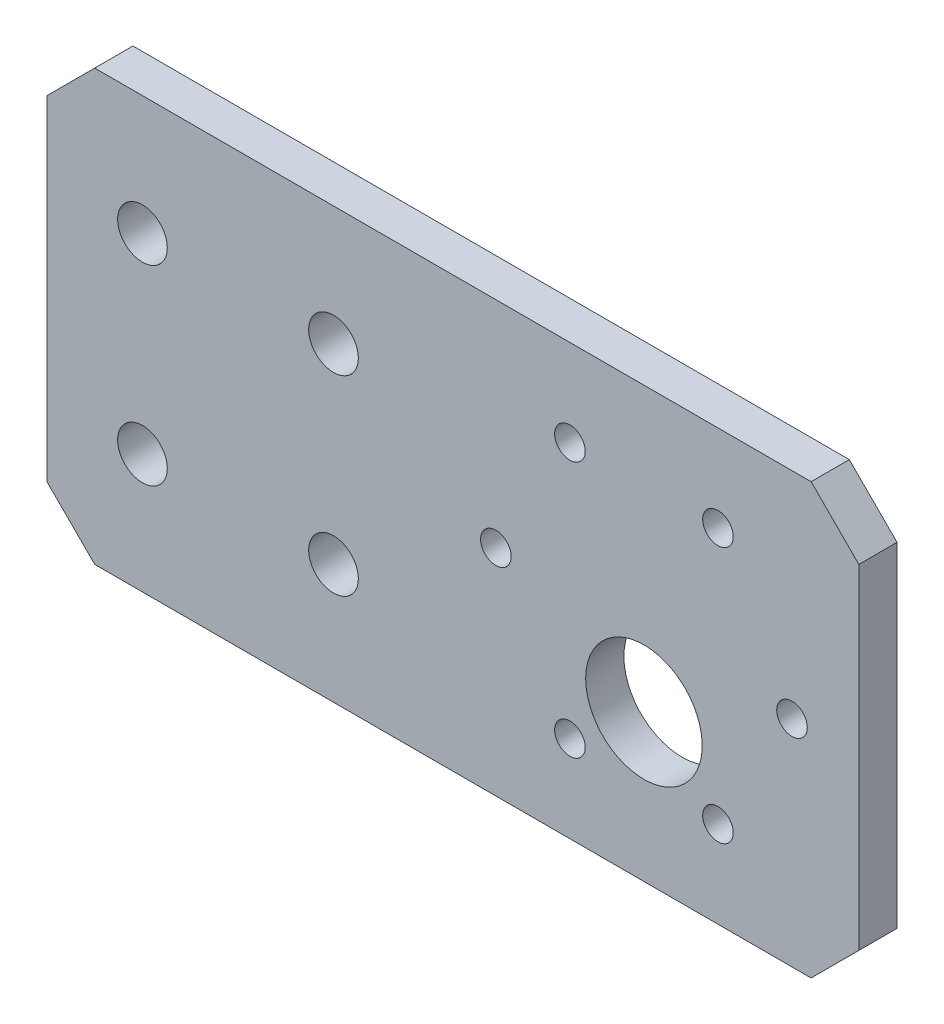
SolidWorks part; units mm, degrees
material "AISI 304"
ref_plane "前基準面" through (0, 0, 0) normal (0, 0, 1) x (1, 0, 0)
ref_plane "上基準面" through (0, 0, 0) normal (0, 1, 0) x (1, 0, 0)
ref_plane "右基準面" through (0, 0, 0) normal (1, 0, 0) x (0, 0, -1)
sketch "Sketch1" plane through (0, 0, 0) normal (0, 0, 1) x (1, 0, 0)
  line L1 (-42.5, -22.5) -> (42.5, -22.5)
  line L2 (-42.5, -22.5) -> (-42.5, 22.5)
  line L3 (-42.5, 22.5) -> (42.5, 22.5)
  line L4 (42.5, -22.5) -> (42.5, 22.5)
  line L5 (-42.5, -22.5) -> (42.5, 22.5) construction
  line L6 (-42.5, 22.5) -> (42.5, -22.5) construction
  point P0 (0, 0)
  dimension "D1" = 45
  dimension "D2" = 85
extrude "Boss-Extrude1" add sketch "Sketch1" along normal blind 4
sketch "Sketch2" plane through (0, 0, 4) normal (0, 0, 1) x (1, 0, 0)
  line L0 (20, 0) -> (20, 22.5) construction
  line L3 (20, 0) -> (35.5, 0) construction
  line L4 (42.5, 22.5) -> (-42.5, 22.5) construction
  line L6 (42.5, -22.5) -> (42.5, 22.5) construction
  circle A4 centre (35.5, 0) radius 1.6
  circle A6 centre (27.75, -13.4234) radius 1.6
  circle A7 centre (12.25, -13.4234) radius 1.6
  circle A8 centre (4.5, 0) radius 1.6
  circle A9 centre (12.25, 13.4234) radius 1.6
  circle A10 centre (27.75, 13.4234) radius 1.6
  dimension "D1" = 15.5
  dimension "D4" = 3.2
  dimension "D5" = 6
  dimension "D2" = 22.5
  dimension "D3" = 22.5
  dimension "D6" = 26.8468
  dimension "D7" = 15.5
sketch "Sketch3" plane through (0, 0, 4) normal (0, 0, 1) x (1, 0, 0)
  line L0 (-32.5, -10) -> (-42.5, -10) construction
  line L1 (-42.5, 22.5) -> (-42.5, -22.5) construction
  line L2 (-42.5, -22.5) -> (42.5, -22.5) construction
  circle A0 centre (-32.5, -10) radius 2.6
  dimension "D1" = 5.2
  dimension "D2" = 10
  dimension "D3" = 12.5
extrude "Cut-Extrude2" cut sketch "Sketch3" against normal through all
chamfer "Chamfer1" distance 5 angle 45 4 edges at (42.5, 22.5, 2) (42.5, -22.5, 2) (-42.5, -22.5, 2) (-42.5, 22.5, 2)
extrude "除料-伸長1" cut sketch "Sketch2" against normal through all
pattern_linear "直線複製排列1" count 2 spacing 20 along (0, 1, 0) count 2 spacing 20 along (1, 0, 0) of "Cut-Extrude2"
sketch "草圖1" plane through (0, 0, 0) normal (0, 0, -1) x (-1, 0, 0)
  line L0 (-20, 22.5) -> (-20, -7.14) construction
  line L1 (-37.5, 22.5) -> (37.5, 22.5) construction
  line L2 (-42.5, -17.5) -> (-42.5, 17.5) construction
  line L3 (37.5, -22.5) -> (-37.5, -22.5) construction
  circle A0 centre (-20, -7.14) radius 6.1
  dimension "D1" = 12.2
  dimension "D2" = 15.36
  dimension "D3" = 22.5
extrude "除料-伸長2" cut sketch "草圖1" against normal through all
